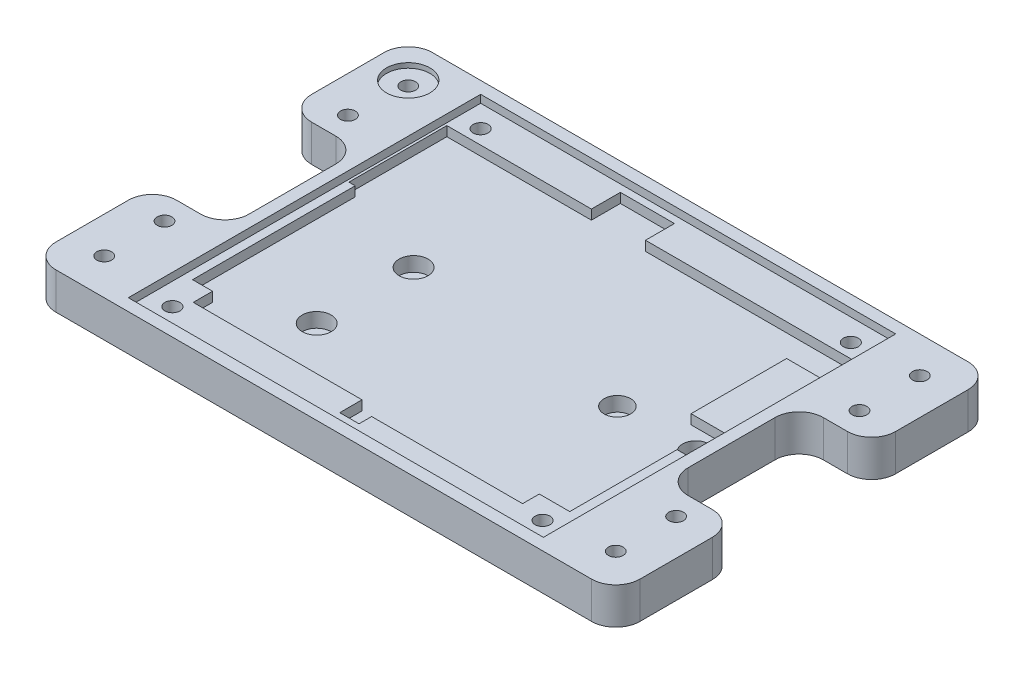
SolidWorks part; units mm, degrees
ref_plane "Front Plane" through (0, 0, 0) normal (0, 0, 1) x (1, 0, 0)
ref_plane "Top Plane" through (0, 0, 0) normal (0, 1, 0) x (1, 0, 0)
ref_plane "Right Plane" through (0, 0, 0) normal (1, 0, 0) x (0, 0, -1)
sketch "Sketch1" plane through (0, 0, 0) normal (0, 1, 0) x (1, 0, 0)
  line L0 (-40.307, 35.3779) -> (-40.307, 7.3779)
  line L1 (-44.307, -17.6221) -> (45.693, -17.6221)
  line L2 (50.693, 7.3779) -> (50.693, 35.3779)
  line L3 (45.693, 60.3779) -> (-44.307, 60.3779)
  line L4 (-44.307, 60.3779) -> (-55.307, 60.3779)
  line L5 (-55.307, 60.3779) -> (-55.307, 35.3779)
  line L6 (-55.307, 35.3779) -> (-40.307, 35.3779)
  line L7 (-44.307, -17.6221) -> (-55.307, -17.6221)
  line L8 (-55.307, -17.6221) -> (-55.307, 7.3779)
  line L9 (-55.307, 7.3779) -> (-40.307, 7.3779)
  line L10 (45.693, -17.6221) -> (65.693, -17.6221)
  line L11 (65.693, -17.6221) -> (65.693, 7.3779)
  line L12 (65.693, 7.3779) -> (50.693, 7.3779)
  line L13 (45.693, 60.3779) -> (65.693, 60.3779)
  line L14 (65.693, 60.3779) -> (65.693, 35.3779)
  line L15 (65.693, 35.3779) -> (50.693, 35.3779)
  dimension "D1" = 78
  dimension "D2" = 91
  dimension "D3" = 15
  dimension "D4" = 25
  dimension "D5" = 25
  dimension "D6" = 15
  dimension "D7" = 25
  dimension "D8" = 25
  dimension "D10" = 15
  dimension "D11" = 15
extrude "Boss-Extrude1" add sketch "Sketch1" along normal blind 7.6
sketch "Sketch2" plane through (0, 7.6, 0) normal (0, 1, 0) x (1, 0, 0)
  line L0 (-37.307, 57.3779) -> (-37.307, -14.6221)
  line L1 (-37.307, -14.6221) -> (47.693, -14.6221)
  line L2 (47.693, -14.6221) -> (47.693, 57.3779)
  line L3 (47.693, 57.3779) -> (-37.307, 57.3779)
  line L4 (-40.307, 35.3779) -> (-40.307, 7.3779) construction
  line L5 (-55.307, -17.6221) -> (65.693, -17.6221) construction
  line L6 (65.693, 60.3779) -> (-55.307, 60.3779) construction
  line L7 (50.693, 7.3779) -> (50.693, 35.3779) construction
  line L9 (-37.807, 57.8779) -> (48.193, 57.8779)
  line L10 (-37.807, 57.8779) -> (-37.807, -15.1221)
  line L11 (-37.807, -15.1221) -> (48.193, -15.1221)
  line L12 (48.193, 57.8779) -> (48.193, -15.1221)
  circle A0 centre (43.465, 53.3139) radius 1.55
  circle A1 centre (-33.243, 53.3139) radius 1.55
  circle A2 centre (-33.243, -10.5581) radius 1.55
  circle A3 centre (43.465, -10.5581) radius 1.55
  dimension "D8" = 85
  dimension "D1" = 3
  dimension "D2" = 3
  dimension "D3" = 72
  dimension "D4" = 63.872
  dimension "D5" = 4.064
  dimension "D6" = 76.708
  dimension "D7" = 4.064
  dimension "D9" = 3
  dimension "D10" = 3
  dimension "D11" = 4.064
  dimension "D12" = 4.228
  dimension "D13" = 3
  dimension "D14" = 0.5
  dimension "D15" = 0.5
  dimension "D16" = 0.5
  dimension "D17" = 0.5
extrude "Cut-Extrude9" cut sketch "Sketch2<5>" against normal blind 1.61 contours L3 L0 L1 L2
sketch "Sketch2<5>" plane through (0, 7.6, 0) normal (0, 1, 0) x (1, 0, 0) same geometry as "Sketch2"
sketch "Sketch11" plane through (0, 5.99, 0) normal (0, 1, 0) x (1, 0, 0)
  line L0 (-35.9992, 50.3779) -> (-7.3511, 50.3779)
  line L1 (-7.3511, 50.3779) -> (-7.3511, 56.3779)
  line L2 (-7.3511, 56.3779) -> (3.8517, 56.3779)
  line L3 (3.8517, 56.3779) -> (3.8517, 50.3779)
  line L4 (3.8517, 50.3779) -> (47.693, 50.3779)
  line L5 (47.693, -14.6221) -> (47.693, 57.3779) construction
  line L6 (47.693, 50.3779) -> (47.693, 43.7779)
  line L7 (47.693, 43.7779) -> (39.693, 43.7779)
  line L8 (39.693, 43.7779) -> (39.693, 23.9779)
  line L9 (39.693, 23.9779) -> (47.693, 23.9779)
  line L10 (47.693, 23.9779) -> (47.693, 16.0779)
  line L11 (47.693, 16.0779) -> (44.693, 16.0779)
  line L12 (44.693, 16.0779) -> (44.693, -6.1562)
  line L13 (38.383, -9.6221) -> (7.111, -9.6221)
  line L14 (-35.9992, -3.6221) -> (-35.9992, 30.0779)
  line L15 (-35.9992, 30.0779) -> (-37.307, 30.0779)
  line L16 (-37.307, 57.3779) -> (-37.307, -14.6221) construction
  line L17 (-37.307, 30.0779) -> (-37.307, 50.3779)
  line L18 (-37.307, 50.3779) -> (-35.9992, 50.3779)
  line L19 (-37.307, -14.6221) -> (47.693, -14.6221) construction
  line L20 (-37.307, -14.6221) -> (47.693, -14.6221) construction
  line L21 (44.693, -6.1562) -> (38.383, -6.1562)
  line L22 (38.383, -6.1562) -> (38.383, -9.6221)
  line L23 (-35.9992, -3.6221) -> (-31.8572, -3.6221)
  line L24 (-31.8572, -3.6221) -> (-31.8572, -7.6221)
  line L25 (3.111, -7.6221) -> (3.111, -12.2378)
  line L26 (3.111, -12.2378) -> (7.111, -12.2378)
  line L27 (7.111, -12.2378) -> (7.111, -9.6221)
  line L28 (3.111, -7.6221) -> (-31.8572, -7.6221)
  line L29 (-37.307, 57.3779) -> (-37.307, -14.6221) construction
  line L30 (47.693, -14.6221) -> (47.693, 57.3779) construction
  point P25 (43.693, 43.7779)
  point P34 (5.111, -12.2378)
  point P37 (38.383, -7.8892)
  point P38 (-33.9282, -3.6221)
  dimension "D1" = 44.7
  dimension "D2" = 65
  dimension "D3" = 71
  dimension "D4" = 65
  dimension "D5" = 58.4
  dimension "D6" = 38.6
  dimension "D7" = 30.7
  dimension "D8" = 5
  dimension "D9" = 3
  dimension "D10" = 9.31
  dimension "D11" = 2
  dimension "D12" = 40.418
  dimension "D13" = 7
  dimension "D14" = 72.3112
  dimension "D15" = 11
  dimension "D16" = 8
extrude "Cut-Extrude10" cut sketch "Sketch11" against normal blind 2
extrude "Cut-Extrude3" cut sketch "Sketch2" against normal through all contours A1 | A0 | A3 | A2
sketch "Sketch4" plane through (-31.1286, 7.6, 0) normal (0, -1, 0) x (-1, 0, 0)
  line L0 (-19.1435, -1.7378) -> (-23.3424, -3.9435)
  line L1 (-3.6123, -3.9435) -> (-7.8102, -1.7378)
  line L2 (-7.8102, -6.1461) -> (-3.6123, -3.9435)
  line L3 (-23.3424, -3.9435) -> (-19.1435, -6.1461)
  line L4 (-19.1435, -7.1869) -> (-23.3424, -9.3906)
  line L5 (-3.6123, -9.3906) -> (-7.8102, -7.1869)
  line L6 (-7.8102, -11.5952) -> (-3.6123, -9.3906)
  line L7 (-23.3424, -9.3906) -> (-19.1435, -11.5952)
  line L8 (-19.1435, -12.635) -> (-23.3424, -14.8387)
  line L9 (-3.6123, -14.8387) -> (-7.8102, -12.635)
  line L10 (-7.8102, -17.0423) -> (-3.6123, -14.8387)
  line L11 (-23.3424, -14.8387) -> (-19.1435, -17.0423)
  line L12 (-7.5017, 11.7391) -> (-4.8823, 11.7391)
  line L13 (-10.0888, 5.39) -> (-10.0888, 7.6364)
  line L14 (-4.8823, 1.2873) -> (-7.5017, 1.2873)
  line L15 (-4.663, 11.5198) -> (-4.663, 1.5066)
  line L16 (-6.3249, 2.5097) -> (-6.3249, 10.5177)
  line L17 (-7.2487, 2.5097) -> (-6.3249, 2.5097)
  line L18 (-8.4041, 7.7514) -> (-8.4041, 5.2749)
  line L19 (-6.3249, 10.5177) -> (-7.2487, 10.5177)
  line L20 (-22.2342, 4.125) -> (-22.2342, 11.5198)
  line L21 (-16.8287, 11.5198) -> (-16.8287, 4.125)
  line L22 (-18.2714, 11.7391) -> (-17.048, 11.7391)
  line L23 (-18.4916, 4.127) -> (-18.4916, 11.5198)
  line L24 (-20.5713, 11.5198) -> (-20.5713, 4.127)
  line L25 (-22.0149, 11.7391) -> (-20.7905, 11.7391)
  line L26 (-14.3304, 10.4184) -> (-14.3304, 1.5066)
  line L27 (-15.903, 10.4184) -> (-14.3304, 10.4184)
  line L28 (-16.1228, 11.5198) -> (-16.1228, 10.6377)
  line L29 (-10.9808, 11.7391) -> (-15.903, 11.7391)
  line L30 (-10.7605, 10.6377) -> (-10.7605, 11.5198)
  line L31 (-12.5529, 10.4184) -> (-10.9808, 10.4184)
  line L32 (-12.5529, 1.5066) -> (-12.5529, 10.4184)
  line L33 (-14.1121, 1.2873) -> (-12.7722, 1.2873)
  spline S0 degree 3 poles (-7.8102, -1.7378) (-13.2484, -3.8532) (-13.7073, -3.8532) (-19.1435, -1.7378) knots 4 4 4 4 5 5 5 5
  spline S1 degree 3 poles (-19.1435, -6.1461) (-13.7073, -4.0318) (-13.2484, -4.0318) (-7.8102, -6.1461) knots 1 1 1 1 2 2 2 2
  spline S2 degree 3 poles (-7.8102, -7.1869) (-13.2484, -9.3013) (-13.7073, -9.3013) (-19.1435, -7.1869) knots 4 4 4 4 5 5 5 5
  spline S3 degree 3 poles (-19.1435, -11.5952) (-13.7073, -9.4799) (-13.2484, -9.4799) (-7.8102, -11.5952) knots 1 1 1 1 2 2 2 2
  spline S4 degree 3 poles (-7.8102, -12.635) (-13.2484, -14.7504) (-13.7073, -14.7504) (-19.1435, -12.635) knots 4 4 4 4 5 5 5 5
  spline S5 degree 3 poles (-19.1435, -17.0423) (-13.7073, -14.928) (-13.2484, -14.928) (-7.8102, -17.0423) knots 1 1 1 1 2 2 2 2
  spline S6 degree 3 poles (-9.5158, 11.0207) (-9.1398, 11.5079) (-8.5192, 11.7391) (-7.5017, 11.7391) knots 10 10 10 10 11 11 11 11
  spline S7 degree 3 poles (-10.0888, 7.6364) (-10.0888, 9.2824) (-10.0709, 10.3559) (-9.5158, 11.0207) knots 9 9 9 9 10 10 10 10
  spline S8 degree 3 poles (-9.5158, 2.0057) (-10.0709, 2.6705) (-10.0888, 3.744) (-10.0888, 5.39) knots 7 7 7 7 8 8 8 8
  spline S9 degree 3 poles (-7.5017, 1.2873) (-8.5192, 1.2873) (-9.1398, 1.5185) (-9.5158, 2.0057) knots 6 6 6 6 7 7 7 7
  spline S10 degree 3 poles (-4.7206, 1.3459) (-4.7558, 1.3112) (-4.8039, 1.2873) (-4.8823, 1.2873) knots 4 4 4 4 5 5 5 5
  spline S11 degree 3 poles (-4.663, 1.5066) (-4.663, 1.4282) (-4.6858, 1.3806) (-4.7206, 1.3459) knots 3 3 3 3 4 4 4 4
  spline S12 degree 3 poles (-4.7206, 11.6815) (-4.6858, 11.6458) (-4.663, 11.5992) (-4.663, 11.5198) knots 1 1 1 1 2 2 2 2
  spline S13 degree 3 poles (-4.8823, 11.7391) (-4.8039, 11.7391) (-4.7558, 11.7152) (-4.7206, 11.6815) knots 0 0 0 0 1 1 1 1
  spline S14 degree 3 poles (-8.0885, 2.8014) (-7.9, 2.5752) (-7.6565, 2.5097) (-7.2487, 2.5097) knots 5 5 5 5 6 6 6 6
  spline S15 degree 3 poles (-8.4041, 5.2749) (-8.4041, 3.8551) (-8.3793, 3.1507) (-8.0885, 2.8014) knots 4 4 4 4 5 5 5 5
  spline S16 degree 3 poles (-8.0885, 10.225) (-8.3793, 9.8757) (-8.4041, 9.1713) (-8.4041, 7.7514) knots 2 2 2 2 3 3 3 3
  spline S17 degree 3 poles (-7.2487, 10.5177) (-7.6565, 10.5177) (-7.9, 10.4512) (-8.0885, 10.225) knots 1 1 1 1 2 2 2 2
  spline S18 degree 3 poles (-21.6364, 1.9045) (-22.1156, 2.4611) (-22.2342, 3.1259) (-22.2342, 4.125) knots 20 20 20 20 21 21 21 21
  spline S19 degree 3 poles (-19.5364, 1.1554) (-20.5658, 1.1554) (-21.2286, 1.4312) (-21.6364, 1.9045) knots 19 19 19 19 20 20 20 20
  spline S20 degree 3 poles (-17.4027, 1.9035) (-17.8467, 1.4143) (-18.5189, 1.1554) (-19.5364, 1.1554) knots 18 18 18 18 19 19 19 19
  spline S21 degree 3 poles (-16.8287, 4.125) (-16.8287, 3.0485) (-16.9751, 2.3738) (-17.4027, 1.9035) knots 17 17 17 17 18 18 18 18
  spline S22 degree 3 poles (-16.8873, 11.6815) (-16.8515, 11.6458) (-16.8287, 11.5992) (-16.8287, 11.5198) knots 15 15 15 15 16 16 16 16
  spline S23 degree 3 poles (-17.048, 11.7391) (-16.9691, 11.7391) (-16.921, 11.7152) (-16.8873, 11.6815) knots 14 14 14 14 15 15 15 15
  spline S24 degree 3 poles (-18.4321, 11.6815) (-18.3984, 11.7152) (-18.3502, 11.7391) (-18.2714, 11.7391) knots 12 12 12 12 13 13 13 13
  spline S25 degree 3 poles (-18.4916, 11.5198) (-18.4916, 11.5992) (-18.4673, 11.6458) (-18.4321, 11.6815) knots 11 11 11 11 12 12 12 12
  spline S26 degree 3 poles (-18.8007, 2.6238) (-18.5636, 2.8848) (-18.4916, 3.3283) (-18.4916, 4.127) knots 9 9 9 9 10 10 10 10
  spline S27 degree 3 poles (-19.5151, 2.344) (-19.2085, 2.344) (-18.9773, 2.4294) (-18.8007, 2.6238) knots 8 8 8 8 9 9 9 9
  spline S28 degree 3 poles (-20.2627, 2.6218) (-20.0925, 2.4353) (-19.8514, 2.344) (-19.5151, 2.344) knots 7 7 7 7 8 8 8 8
  spline S29 degree 3 poles (-20.5713, 4.127) (-20.5713, 3.3561) (-20.5127, 2.8977) (-20.2627, 2.6218) knots 6 6 6 6 7 7 7 7
  spline S30 degree 3 poles (-20.6298, 11.6815) (-20.5946, 11.6458) (-20.5713, 11.5992) (-20.5713, 11.5198) knots 4 4 4 4 5 5 5 5
  spline S31 degree 3 poles (-20.7905, 11.7391) (-20.7122, 11.7391) (-20.6645, 11.7152) (-20.6298, 11.6815) knots 3 3 3 3 4 4 4 4
  spline S32 degree 3 poles (-22.1756, 11.6815) (-22.1414, 11.7152) (-22.0928, 11.7391) (-22.0149, 11.7391) knots 1 1 1 1 2 2 2 2
  spline S33 degree 3 poles (-22.2342, 11.5198) (-22.2342, 11.5992) (-22.2104, 11.6458) (-22.1756, 11.6815) knots 0 0 0 0 1 1 1 1
  spline S34 degree 3 poles (-16.0652, 10.476) (-16.03, 10.4413) (-15.9819, 10.4184) (-15.903, 10.4184) knots 17 17 17 17 18 18 18 18
  spline S35 degree 3 poles (-16.1228, 10.6377) (-16.1228, 10.5593) (-16.0985, 10.5107) (-16.0652, 10.476) knots 16 16 16 16 17 17 17 17
  spline S36 degree 3 poles (-16.0652, 11.6815) (-16.0985, 11.6458) (-16.1228, 11.5992) (-16.1228, 11.5198) knots 14 14 14 14 15 15 15 15
  spline S37 degree 3 poles (-15.903, 11.7391) (-15.9819, 11.7391) (-16.03, 11.7152) (-16.0652, 11.6815) knots 13 13 13 13 14 14 14 14
  spline S38 degree 3 poles (-10.819, 11.6815) (-10.8548, 11.7152) (-10.9019, 11.7391) (-10.9808, 11.7391) knots 11 11 11 11 12 12 12 12
  spline S39 degree 3 poles (-10.7605, 11.5198) (-10.7605, 11.5992) (-10.7843, 11.6458) (-10.819, 11.6815) knots 10 10 10 10 11 11 11 11
  spline S40 degree 3 poles (-10.819, 10.476) (-10.7843, 10.5107) (-10.7605, 10.5593) (-10.7605, 10.6377) knots 8 8 8 8 9 9 9 9
  spline S41 degree 3 poles (-10.9808, 10.4184) (-10.9019, 10.4184) (-10.8548, 10.4413) (-10.819, 10.476) knots 7 7 7 7 8 8 8 8
  spline S42 degree 3 poles (-12.6114, 1.3459) (-12.5757, 1.3806) (-12.5529, 1.4282) (-12.5529, 1.5066) knots 4 4 4 4 5 5 5 5
  spline S43 degree 3 poles (-12.7722, 1.2873) (-12.6943, 1.2873) (-12.6457, 1.3112) (-12.6114, 1.3459) knots 3 3 3 3 4 4 4 4
  spline S44 degree 3 poles (-14.2729, 1.3459) (-14.2376, 1.3112) (-14.19, 1.2873) (-14.1121, 1.2873) knots 1 1 1 1 2 2 2 2
  spline S45 degree 3 poles (-14.3304, 1.5066) (-14.3304, 1.4282) (-14.3076, 1.3806) (-14.2729, 1.3459) knots 0 0 0 0 1 1 1 1
extrude "Boss-Extrude2" [suppressed] add sketch "Sketch4" against normal blind 1.6
fillet "Fillet1" radius 5 12 edges at (-55.307, 3.8, -35.3779) (-55.307, 3.8, -60.3779) (-55.307, 3.8, 17.6221) (65.693, 3.8, -60.3779) (50.693, 3.8, -35.3779) (65.693, 3.8, -35.3779) (65.693, 3.8, 17.6221) (-55.307, 3.8, -7.3779) (65.693, 3.8, -7.3779) (50.693, 3.8, -7.3779) (-40.307, 3.8, -7.3779) (-40.307, 3.8, -35.3779)
sketch "Sketch5" plane through (0, 7.6, 0) normal (0, 1, 0) x (1, 0, 0)
  line L0 (60.693, 60.3779) -> (-50.307, 60.3779) construction
  line L1 (-55.307, 55.3779) -> (-55.307, 40.3779) construction
  line L3 (-55.307, 2.3779) -> (-55.307, -12.6221) construction
  line L5 (65.693, -12.6221) -> (65.693, 2.3779) construction
  line L6 (65.693, 40.3779) -> (65.693, 55.3779) construction
  line L7 (-50.307, 35.3779) -> (-45.307, 35.3779) construction
  line L9 (55.693, 35.3779) -> (60.693, 35.3779) construction
  line L10 (-45.307, 7.3779) -> (-50.307, 7.3779) construction
  line L11 (-50.307, -17.6221) -> (60.693, -17.6221) construction
  line L12 (60.693, 7.3779) -> (55.693, 7.3779) construction
  circle A0 centre (-47.807, 52.8779) radius 1.525
  circle A1 centre (-47.807, 52.8779) radius 4.5
  circle A2 centre (-47.807, -10.1221) radius 1.525
  circle A3 centre (58.193, -10.1221) radius 1.525
  circle A4 centre (58.193, 52.8779) radius 1.525
  circle A5 centre (-47.807, 40.3779) radius 1.525
  circle A6 centre (-47.807, 2.3779) radius 1.525
  circle A7 centre (58.193, 2.3779) radius 1.525
  circle A8 centre (58.193, 40.3779) radius 1.525
  circle A9 centre (-47.807, 40.3779) radius 3.5
  dimension "D1" = 3.05
  dimension "D4" = 9
  dimension "D7" = 3.05
  dimension "D10" = 3.05
  dimension "D13" = 3.05
  dimension "D14" = 3.05
  dimension "D20" = 3.05
  dimension "D23" = 3.05
  dimension "D24" = 3.05
  dimension "D28" = 7
  dimension "D2" = 7.5
  dimension "D3" = 7.5
  dimension "D5" = 5
  dimension "D6" = 7.5
  dimension "D8" = 7.5
  dimension "D9" = 7.5
  dimension "D11" = 7.5
  dimension "D12" = 7.5
  dimension "D15" = 5
  dimension "D16" = 7.5
  dimension "D17" = 12.5
  dimension "D18" = 7.5
  dimension "D19" = 7.5
  dimension "D21" = 7.5
  dimension "D22" = 5
  dimension "D25" = 7.5
  dimension "D26" = 5
  dimension "D27" = 12.5
extrude "Cut-Extrude4" cut sketch "Sketch5" against normal blind 10 contours A0 | A2 | A3 | A4 | A5 | A6 | A8 | A7
extrude "Cut-Extrude5" cut sketch "Sketch5<3>" against normal blind 1 contours A1
sketch "Sketch5<3>" plane through (0, 7.6, 0) normal (0, 1, 0) x (1, 0, 0) same geometry as "Sketch5"
sketch "Sketch6" plane through (0, 0, 0) normal (0, -1, 0) x (1, 0, 0)
  line L1 (-48.0631, 6.9281) -> (-45.169, 8.3033)
  line L2 (-45.169, 8.3033) -> (-44.9128, 11.4973)
  line L3 (-44.9128, 11.4973) -> (-47.5509, 13.3162)
  line L4 (-47.5509, 13.3162) -> (-50.4451, 11.9409)
  line L5 (-50.4451, 11.9409) -> (-50.7012, 8.7469)
  line L6 (-50.7012, 8.7469) -> (-48.0631, 6.9281)
  line L7 (57.9947, 6.924) -> (60.8635, 8.3513)
  line L8 (60.8635, 8.3513) -> (61.0618, 11.5494)
  line L9 (61.0618, 11.5494) -> (58.3913, 13.3203)
  line L10 (58.3913, 13.3203) -> (55.5225, 11.8929)
  line L11 (55.5225, 11.8929) -> (55.3241, 8.6948)
  line L12 (55.3241, 8.6948) -> (57.9947, 6.924)
  line L13 (60.5667, -50.7254) -> (57.5157, -49.746)
  line L14 (57.5157, -49.746) -> (55.142, -51.8984)
  line L15 (55.142, -51.8984) -> (55.8193, -55.0304)
  line L16 (55.8193, -55.0304) -> (58.8702, -56.0098)
  line L17 (58.8702, -56.0098) -> (61.2439, -53.8573)
  line L18 (61.2439, -53.8573) -> (60.5667, -50.7254)
  line L19 (-51.0113, -52.8749) -> (-49.4118, -55.6514)
  line L20 (-49.4118, -55.6514) -> (-46.2075, -55.6544)
  line L21 (-46.2075, -55.6544) -> (-44.6027, -52.8809)
  line L22 (-44.6027, -52.8809) -> (-46.2023, -50.1044)
  line L23 (-46.2023, -50.1044) -> (-49.4066, -50.1014)
  line L24 (-49.4066, -50.1014) -> (-51.0113, -52.8749)
  line L25 (-36.1686, 11.8651) -> (-35.8377, 8.678)
  line L26 (-35.8377, 8.678) -> (-32.9121, 7.371)
  line L27 (-32.9121, 7.371) -> (-30.3174, 9.2511)
  line L28 (-30.3174, 9.2511) -> (-30.6483, 12.4383)
  line L29 (-30.6483, 12.4383) -> (-33.5739, 13.7453)
  line L30 (-33.5739, 13.7453) -> (-36.1686, 11.8651)
  line L31 (40.2673, 10.7639) -> (41.6879, 7.8918)
  line L32 (41.6879, 7.8918) -> (44.8856, 7.6859)
  line L33 (44.8856, 7.6859) -> (46.6627, 10.3523)
  line L34 (46.6627, 10.3523) -> (45.2421, 13.2245)
  line L35 (45.2421, 13.2245) -> (42.0444, 13.4303)
  line L36 (42.0444, 13.4303) -> (40.2673, 10.7639)
  line L37 (40.9857, -55.3439) -> (43.9834, -56.476)
  line L38 (43.9834, -56.476) -> (46.4626, -54.446)
  line L39 (46.4626, -54.446) -> (45.9442, -51.2839)
  line L40 (45.9442, -51.2839) -> (42.9466, -50.1518)
  line L41 (42.9466, -50.1518) -> (40.4673, -52.1818)
  line L42 (40.4673, -52.1818) -> (40.9857, -55.3439)
  line L43 (-36.4262, -53.6809) -> (-34.5167, -56.2541)
  line L44 (-34.5167, -56.2541) -> (-31.3335, -55.8871)
  line L45 (-31.3335, -55.8871) -> (-30.0598, -52.9468)
  line L46 (-30.0598, -52.9468) -> (-31.9693, -50.3736)
  line L47 (-31.9693, -50.3736) -> (-35.1525, -50.7407)
  line L48 (-35.1525, -50.7407) -> (-36.4262, -53.6809)
  circle A0 centre (-47.807, 10.1221) radius 2.775 construction
  circle A1 centre (58.193, 10.1221) radius 2.775 construction
  circle A2 centre (58.193, -52.8779) radius 2.775 construction
  circle A3 centre (-47.807, -52.8779) radius 2.775 construction
  circle A4 centre (58.193, -52.8779) radius 1.525 construction
  circle A5 centre (-33.243, 10.5581) radius 2.775 construction
  circle A6 centre (43.465, 10.5581) radius 2.775 construction
  circle A7 centre (43.465, -53.3139) radius 2.775 construction
  circle A8 centre (-33.243, -53.3139) radius 2.775 construction
  point P40 (-50.2089, -51.4881)
  dimension "D1" = 5.55
  dimension "D2" = 5.55
  dimension "D3" = 5.55
  dimension "D4" = 5.55
  dimension "D5" = 5.55
  dimension "D6" = 5.55
  dimension "D7" = 5.55
  dimension "D8" = 5.55
extrude "Cut-Extrude6" cut sketch "Sketch6" against normal blind 2.4
sketch "Sketch10" plane through (0, 0, 0) normal (0, -1, 0) x (1, 0, 0)
  line L0 (25.693, -35.3779) -> (25.693, -29.8779)
  line L1 (25.693, -29.8779) -> (20.693, -29.8779)
  line L2 (20.693, -29.8779) -> (20.693, -35.3779)
  line L3 (20.693, -35.3779) -> (25.693, -35.3779)
  line L4 (-16.807, 64.8621) -> (-16.807, -60.1379) construction
  line L7 (25.693, -17.8779) -> (25.693, -12.3779)
  line L8 (25.693, -12.3779) -> (20.693, -12.3779)
  line L9 (20.693, -12.3779) -> (20.693, -17.8779)
  line L10 (20.693, -17.8779) -> (25.693, -17.8779)
  line L11 (50.693, -12.3779) -> (50.693, -30.3779) construction
  line L12 (60.693, -60.3779) -> (-50.307, -60.3779) construction
  line L13 (-50.307, 17.6221) -> (60.693, 17.6221) construction
  line L15 (-54.307, -17.8779) -> (-59.307, -17.8779)
  line L16 (-54.307, -12.3779) -> (-54.307, -17.8779)
  line L17 (-59.307, -12.3779) -> (-54.307, -12.3779)
  line L18 (-59.307, -17.8779) -> (-59.307, -12.3779)
  line L19 (-54.307, -35.3779) -> (-59.307, -35.3779)
  line L20 (-54.307, -29.8779) -> (-54.307, -35.3779)
  line L21 (-59.307, -29.8779) -> (-54.307, -29.8779)
  line L22 (-59.307, -35.3779) -> (-59.307, -29.8779)
  dimension "D1" = 5
  dimension "D2" = 5.5
  dimension "D3" = 5.5
  dimension "D4" = 25
  dimension "D5" = 25
  dimension "D6" = 5
  dimension "D7" = 25
  dimension "D8" = 30
extrude "Cut-Extrude8" [suppressed] cut sketch "Sketch10" against normal blind 5
fillet "Fillet7" [suppressed] radius 1
sketch "Sketch12" plane through (0, 5.99, 0) normal (0, 1, 0) x (1, 0, 0)
  line L0 (47.693, -14.6221) -> (47.693, 57.3779) construction
  line L1 (47.693, 23.9779) -> (47.693, 43.7779) construction
  line L2 (-37.307, -14.6221) -> (47.693, -14.6221) construction
  line L3 (-37.307, -14.6221) -> (47.693, -14.6221) construction
  circle A0 centre (28.733, 19.6679) radius 2.75
  circle A1 centre (44.993, 19.6679) radius 2.75
  circle A2 centre (-17.3054, 3.4079) radius 3
  circle A3 centre (-17.3054, 23.4779) radius 3
  dimension "D1" = 5.5
  dimension "D2" = 5.5
  dimension "D6" = 6
  dimension "D7" = 6
  dimension "D3" = 18.96
  dimension "D4" = 2.7
  dimension "D5" = 34.29
  dimension "D8" = 18.03
  dimension "D9" = 38.1
extrude "Cut-Extrude11" cut sketch "Sketch12" against normal blind 5
extrude "Cut-Extrude12" cut sketch "Sketch2<6>" against normal blind 1.61 contours L10 L11 L12 L9
sketch "Sketch2<6>" plane through (0, 7.6, 0) normal (0, 1, 0) x (1, 0, 0) same geometry as "Sketch2"
equation "\"1.6.00mm\"=2"
